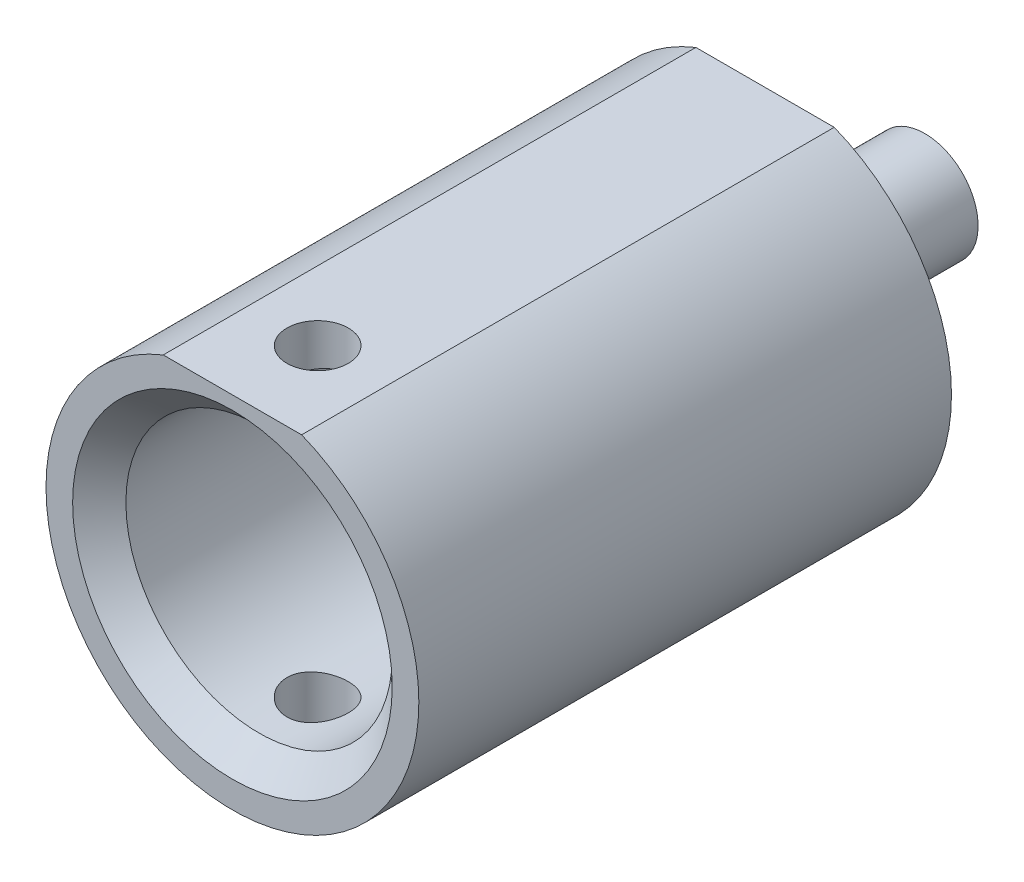
SolidWorks part; units mm, degrees
material "6061 Alloy"
ref_plane "Front Plane" through (0, 0, 0) normal (0, 0, 1) x (1, 0, 0)
ref_plane "Top Plane" through (0, 0, 0) normal (0, 1, 0) x (1, 0, 0)
ref_plane "Right Plane" through (0, 0, 0) normal (1, 0, 0) x (0, 0, -1)
sketch "Sketch1" plane through (0, 0, 0) normal (0, 1, 0) x (1, 0, 0)
  line L6 (0, 0) -> (7.9375, 0)
  line L7 (7.9375, 0) -> (11.1125, 0)
  line L8 (11.1125, 0) -> (11.1125, 31.75)
  line L9 (11.1125, 31.75) -> (3.175, 31.75)
  line L10 (3.175, 31.75) -> (3.175, 41.275)
  line L11 (3.175, 41.275) -> (0, 41.275)
  line L12 (0, 41.275) -> (0, 25.4)
  line L13 (0, 25.4) -> (0, 0)
  line L14 (0, 25.4) -> (7.9375, 25.4) construction
  line L15 (7.9375, 25.4) -> (7.9375, 0) construction
  dimension "D1" = 3.175
  dimension "D2" = 7.9375
  dimension "D3" = 6.35
  dimension "D4" = 25.4
  dimension "D5" = 9.525
revolve "Revolve1" add sketch "Sketch1" angle 360 about L13
hole_wizard "5/8 (0.625) Diameter Hole1" positions "Sketch6" profile "Sketch7" hole size "5/8" standard "ANSI Inch"
sketch "Sketch6" plane through (0, 0, 0) normal (0, 0, 1) x (1, 0, 0)
  point P0 (0, 0)
sketch "Sketch7" plane through (0, 0, 0) normal (1, 0, 0) x (0, -1, 0)
  line L0 (0, 0) -> (0, 30.1693)
  line L1 (0, 30.1693) -> (7.9375, 25.4)
  line L2 (7.9375, 25.4) -> (7.9375, 0)
  line L5 (7.9375, 0) -> (0, 0)
  line L10 (0, 30.1693) -> (-7.9375, 25.4) construction
  line L11 (0, -6.35) -> (0, 107.95) construction
  dimension "Hole Dia." = 15.875
  dimension "Hole Depth" = 25.4
  dimension "Drill Angle" = 118
sketch "Sketch3" plane through (0, 0, 0) normal (1, 0, 0) x (0, 0, -1)
  line L0 (0, 10.3188) -> (0, 11.1125)
  line L1 (0, 11.1125) -> (0, -11.1125) construction
  line L2 (0, 11.1125) -> (31.75, 11.1125)
  line L3 (31.75, 11.1125) -> (31.75, 10.3188)
  line L4 (31.75, -11.1125) -> (31.75, 11.1125) construction
  line L5 (31.75, 10.3188) -> (0, 10.3188)
  dimension "D1" = 0.7937
extrude "Cut-Extrude1" cut sketch "Sketch3" against normal through all both and the other way through all
hole_wizard "#6 Clearance Hole1" positions "Sketch4" profile "Sketch5" hole size "#6" standard "ANSI Inch" end condition through all
sketch "Sketch4" plane through (0, 10.3188, 0) normal (0, 1, 0) x (1, 0, 0)
  line L1 (7.9375, 25.4) -> (-7.9375, 25.4) construction
  point P0 (0, 5.08)
  dimension "D1" = 20.32
sketch "Sketch5" plane through (0, 10.3188, -5.08) normal (1, 0, 0) x (0, 0, 1)
  line L0 (0, 0) -> (0, 21.4313)
  line L1 (0, 21.4313) -> (1.8288, 21.4313)
  line L2 (1.8288, 21.4313) -> (1.8288, 0)
  line L5 (1.8288, 0) -> (0, 0)
  line L11 (0, -6.35) -> (0, 107.95) construction
  dimension "Thru Hole Dia." = 3.6576
  dimension "Thru Hole Depth" = 21.4313
chamfer "Chamfer1" distance 1.5875 angle 45 1 edges at (7.9375, 0, 0)
